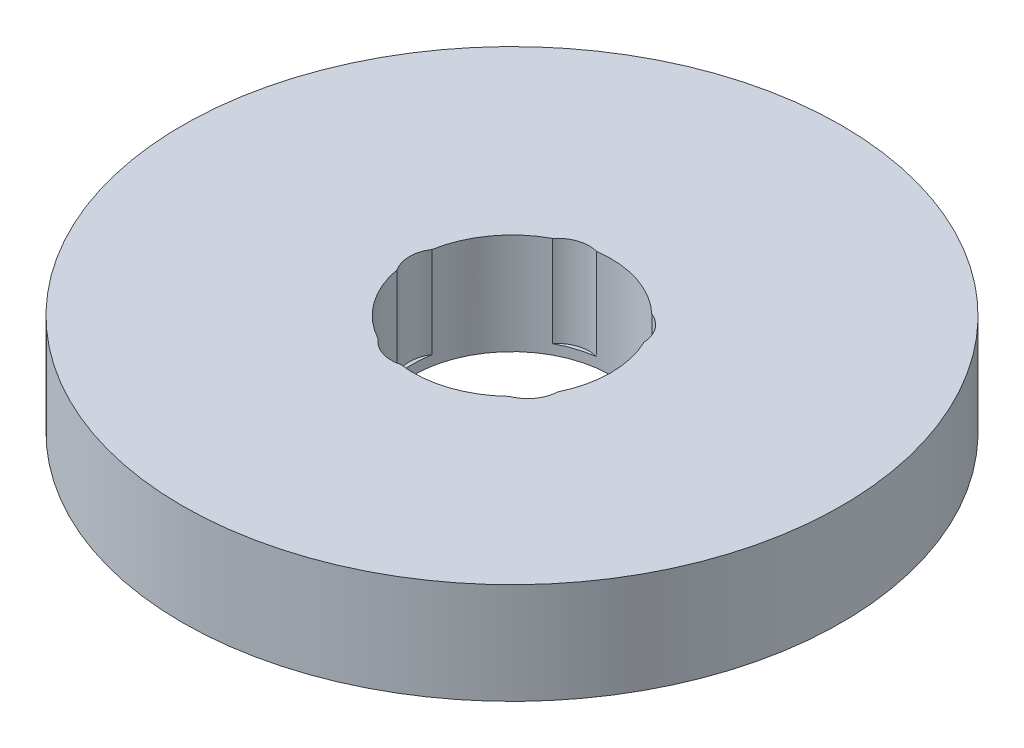
SolidWorks part; units mm, degrees
ref_plane "Front Plane" through (0, 0, 0) normal (0, 0, 1) x (1, 0, 0)
ref_plane "Top Plane" through (0, 0, 0) normal (0, 1, 0) x (1, 0, 0)
ref_plane "Right Plane" through (0, 0, 0) normal (1, 0, 0) x (0, 0, -1)
sketch "Sketch1" plane through (0, 0, 0) normal (0, 1, 0) x (1, 0, 0)
  circle A0 centre (0, 0) radius 75
  dimension "FLANGE_OD" = 150
extrude "Boss-Extrude1" add sketch "Sketch1" along normal blind 23
sketch "Sketch2" plane through (0, 0, 0) normal (0, 1, 0) x (1, 0, 0)
  circle A0 centre (0, 0) radius 22.5
  dimension "BORE_D" = 45
extrude "Cut-Extrude1" cut sketch "Sketch2" along normal through all
sketch "Sketch3" plane through (0, 23, 0) normal (0, 1, 0) x (1, 0, 0)
  circle A0 centre (0, 0) radius 16.0066 construction
  circle A1 centre (-16.0066, 0) radius 7.3145
  dimension "BOLT_D" = 14.629
  dimension "BOLT_PCD" = 32.0131
extrude "Cut-Extrude2" cut sketch "Sketch3" against normal blind 20.74
pattern_circular "CirPattern1" count 5 over 360 about axis through (0, 0, 0) along (0, 1, 0) of "Cut-Extrude2"
